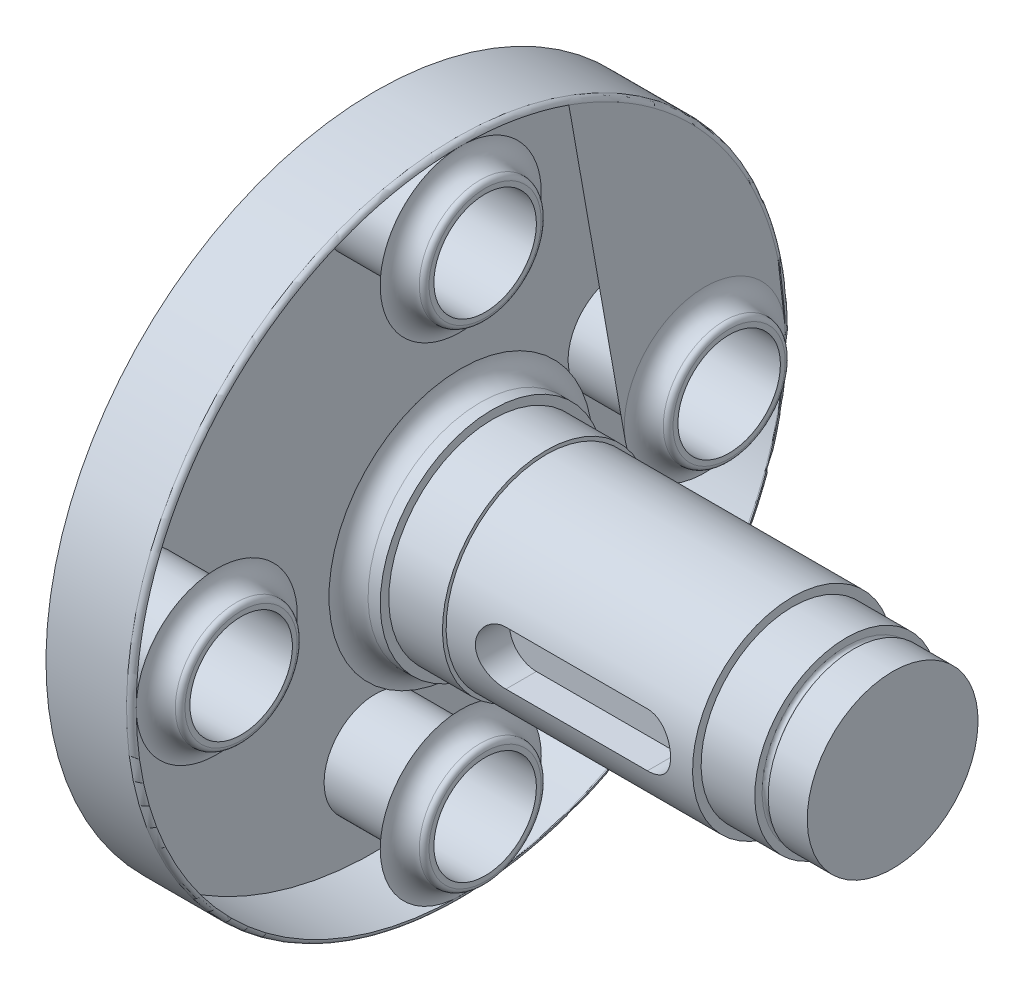
SolidWorks part; units mm, degrees
ref_plane "Piano frontale" through (0, 0, 0) normal (0, 0, 1) x (1, 0, 0)
ref_plane "Piano superiore" through (0, 0, 0) normal (0, 1, 0) x (1, 0, 0)
ref_plane "Piano destro" through (0, 0, 0) normal (1, 0, 0) x (0, 0, -1)
sketch "Schizzo1" plane through (0, 0, 0) normal (0, 0, 1) x (1, 0, 0)
  line L0 (0, 135) -> (35, 135)
  line L6 (35, 46) -> (48, 46)
  line L7 (48, 46) -> (48, 42.5)
  line L8 (48, 42.5) -> (70, 42.5)
  line L9 (70, 42.5) -> (70, 41)
  line L10 (70, 41) -> (171, 41)
  line L11 (171, 41) -> (171, 37.5)
  line L12 (171, 37.5) -> (193, 37.5)
  line L13 (193, 37.5) -> (193, 33)
  line L14 (193, 33) -> (196, 33)
  line L15 (196, 33) -> (196, 35)
  line L16 (196, 35) -> (212, 35)
  line L17 (212, 35) -> (212, 0)
  line L18 (212, 0) -> (0, 0)
  line L19 (0, 0) -> (0, 135)
  line L20 (35, 135) -> (35, 46)
  line L21 (333.3874, 0) -> (-333.3874, 0) construction
  point P5 (0, 0)
  dimension "D1" = 212
  dimension "D2" = 70
  dimension "D3" = 75
  dimension "D4" = 82
  dimension "D5" = 85
  dimension "D6" = 92
  dimension "D7" = 66
  dimension "D8" = 270
  dimension "D9" = 35
  dimension "D10" = 48
  dimension "D11" = 22
  dimension "D12" = 123
  dimension "D13" = 145
  dimension "D14" = 3
revolve "Rivoluzione1" add sketch "Schizzo1" angle 360 about L21
cosmetic thread "Filettatura cosmetica1" parameters "D1"=16, "D2"=68
sketch "Schizzo3" plane through (35, 0, 0) normal (1, 0, 0) x (0, 0, -1)
  circle A0 centre (0, 100) radius 25
  circle A1 centre (0, 100) radius 21
  dimension "D1" = 50
  dimension "D2" = 42
  dimension "D3" = 100
extrude "Taglio-Estrusione4" cut sketch "Schizzo3" against normal up to next contours A1 region at (35, 100, 0)
extrude "Estrusione-Estrusione2" add sketch "Schizzo3<5>" along normal blind 10
sketch "Schizzo3<5>" plane through (35, 0, 0) normal (1, 0, 0) x (0, 0, -1) same geometry as "Schizzo3"
pattern_circular "RipetizioneCircolare1" count 4 every 90 about axis through (333.3874, 0, 0) along (1, 0, 0) of "Taglio-Estrusione4", "Estrusione-Estrusione2" reverse direction yes
sketch "Schizzo5" plane through (0, 0, 0) normal (0, 0, 1) x (1, 0, 0)
  line L0 (93, 0) -> (151, 0) construction
  line L1 (93, 11) -> (151, 11)
  line L2 (93, -11) -> (151, -11)
  line L3 (171, -37.5) -> (171, 37.5) construction
  arc A0 (93, 11) -> (93, -11) centre (93, 0) ccw
  arc A1 (151, -11) -> (151, 11) centre (151, 0) ccw
  point P2 (122, 0)
  dimension "D2" = 11
  dimension "D1" = 58
  dimension "D3" = 20
extrude "Taglio-Estrusione5" cut sketch "Schizzo5" along normal up to next from offset 27
fillet "Raccordo1" radius 1.5 2 edges at (193, 33, 0) (196, 33, 0)
fillet "Raccordo2" radius 8 5 edges at (35, 46, 0) (35, -125, 0) (35, 0, -125) (35, 125, 0) (35, 0, 125)
fillet "Raccordo3" radius 2 5 edges at (35, 135, 0) (45, 125, 0) (45, -125, 0) (45, 0, -125) (45, 0, 125)
